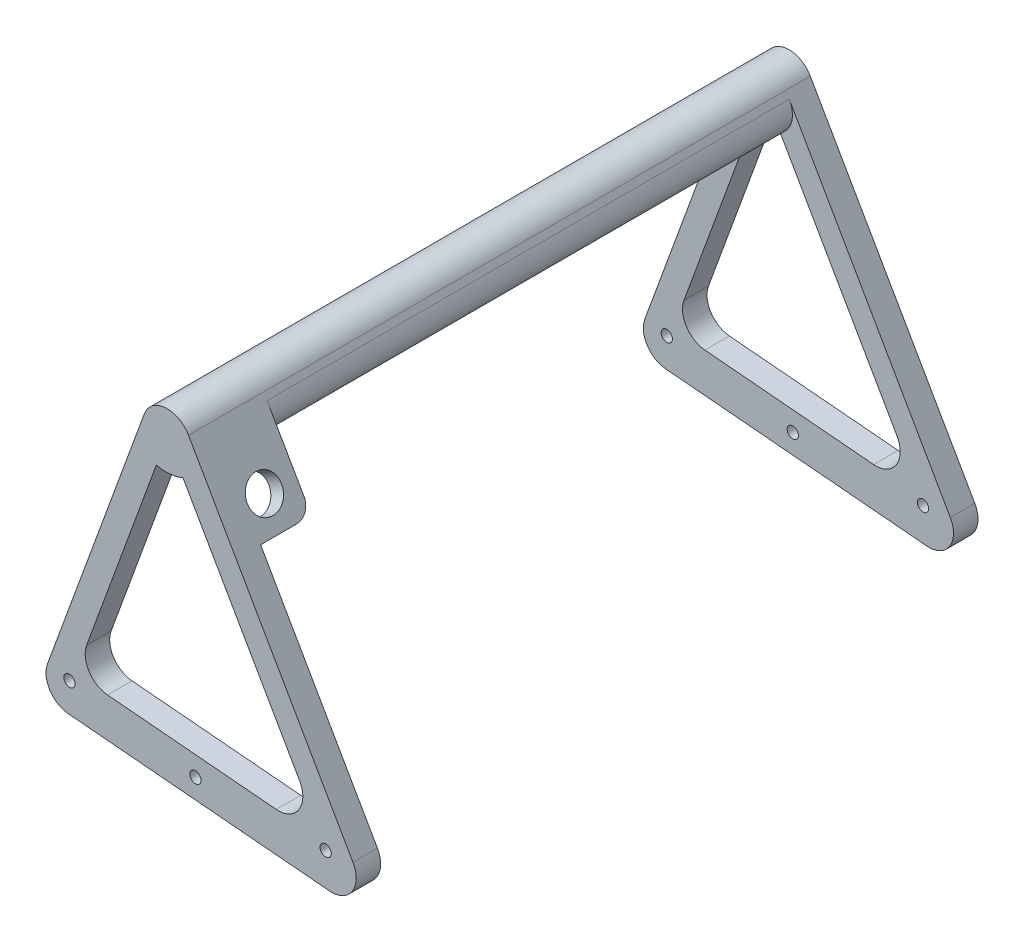
SolidWorks part; units mm, degrees
ref_plane "Ebene vorne" through (0, 0, 0) normal (0, 0, 1) x (1, 0, 0)
ref_plane "Ebene oben" through (0, 0, 0) normal (0, 1, 0) x (1, 0, 0)
ref_plane "Ebene rechts" through (0, 0, 0) normal (1, 0, 0) x (0, 0, -1)
sketch "Skizze1" plane through (0, 0, 0) normal (0, 0, 1) x (1, 0, 0)
  line L0 (-19.2398, 13.5756) -> (6.4562, 83.8896)
  line L1 (6.4562, 83.8896) -> (50.1306, 7.5064)
  line L2 (50.1306, 7.5064) -> (-19.2398, 13.5756)
  line L3 (-11.2375, 20.906) -> (7.458, 72.0643)
  line L4 (7.458, 72.0643) -> (39.2342, 16.4903)
  line L5 (39.2342, 16.4903) -> (-11.2375, 20.906)
  line L8 (-59.2271, -37.2786) -> (110.126, -52.095) construction
  dimension "D1" = 5
  dimension "D2" = 5
  dimension "D3" = 8
extrude "Aufsatz-Linear austragen1" add sketch "Skizze1" along normal blind 5
sketch "Skizze2" plane through (0, 0, -117) normal (0, 0, -1) x (-1, 0, 0)
  line L0 (-50.1306, 7.5064) -> (19.2398, 13.5756)
  line L1 (19.2398, 13.5756) -> (-6.4562, 83.8896)
  line L2 (-6.4562, 83.8896) -> (-50.1306, 7.5064)
  line L3 (-39.2342, 16.4903) -> (11.2375, 20.906)
  line L4 (11.2375, 20.906) -> (-7.458, 72.0643)
  line L5 (-7.458, 72.0643) -> (-39.2342, 16.4903)
extrude "Aufsatz-Linear austragen2" add sketch "Skizze2" along normal blind 5
sketch "Skizze3" plane through (0, 0, 5) normal (0, 0, 1) x (1, 0, 0)
  line L0 (6.4562, 83.8896) -> (-0.4087, 65.1047)
  line L4 (50.1306, 7.5064) -> (6.4562, 83.8896) construction
  line L5 (16.3835, 66.5274) -> (6.4562, 83.8896)
  line L6 (16.3835, 66.5274) -> (-0.4087, 65.1047)
  line L8 (6.4562, 83.8896) -> (-19.2398, 13.5756) construction
  dimension "D1" = 20
  dimension "D2" = 20
extrude "Aufsatz-Linear austragen3" add sketch "Skizze3" against normal through all
fillet "Verrundung1" radius 5 8 edges at (39.2342, 16.4903, 2.5) (-11.2375, 20.906, 2.5) (-11.2375, 20.906, -119.5) (50.1306, 7.5064, -119.5) (39.2342, 16.4903, -119.5) (-19.2398, 13.5756, -119.5) (-19.2398, 13.5756, 2.5) (50.1306, 7.5064, 2.5)
sketch "Skizze4" plane through (0, 0, 5) normal (0, 0, 1) x (1, 0, 0)
  line L0 (13.9446, 21.1239) -> (12.9412, 7.4943) construction
  line L1 (-16.5227, 15.3041) -> (-8.5204, 22.6346) construction
  line L2 (34.3616, 19.6088) -> (45.258, 10.625) construction
  line L3 (1.1405, 21.7125) -> (-1.0929, 8.0856) construction
  line L4 (12.4885, 18.8303) -> (13.9356, 10.6731) construction
  line L5 (-4.7375, 20.3373) -> (29.7145, 17.3232) construction
  line L6 (-12.7398, 13.0069) -> (40.6109, 8.3393) construction
  circle A0 centre (-12.5215, 18.9693) radius 1.15
  circle A1 centre (39.8098, 15.1169) radius 1.15
  arc A2 (-17.0002, 19.7041) -> (-12.7398, 13.0069) centre (-12.304, 17.9879) ccw construction
  arc A3 (-8.9979, 27.0345) -> (-4.7375, 20.3373) centre (-4.3017, 25.3183) ccw construction
  arc A4 (29.7145, 17.3232) -> (34.4908, 24.786) centre (30.1503, 22.3041) ccw construction
  arc A5 (40.6109, 8.3393) -> (45.3873, 15.8021) centre (41.0467, 13.3203) ccw construction
  circle A6 centre (13.2121, 14.7517) radius 1.15
  dimension "D1" = 2.3
extrude "Schnitt-Linear austragen1" cut sketch "Skizze4" against normal through all
fillet "Verrundung2" radius 5 3 edges at (6.4562, 83.8896, -58.5) (-0.4087, 65.1047, -58.5) (16.3835, 66.5274, -58.5)
sketch "Skizze5" plane through (41.0138, 23.4509, 0) normal (0.8681, 0.4964, 0) x (0, 0, -1)
  line L1 (0, 57.4569) -> (10.359, 57.4569)
  line L2 (0, 57.4569) -> (0, 39.2569)
  line L3 (0, 39.2569) -> (10.359, 39.2569)
  line L4 (10.359, 57.4569) -> (10.359, 39.2569)
  line L5 (1.001, 39.2569) -> (6.859, 39.2569) construction
  line L6 (7.359, 39.7569) -> (7.359, 51.4569) construction
  dimension "D1" = 3
extrude "Aufsatz-Linear austragen4" add sketch "Skizze5" against normal up to surface (3 mm away)
sketch "Skizze6" plane through (41.0138, 23.4509, 0) normal (0.8681, 0.4964, 0) x (0, 0, -1)
  circle A0 centre (3.93, 45.6069) radius 3.5
  dimension "D1" = 7
extrude "Schnitt-Linear austragen2" cut sketch "Skizze6" against normal through all
fillet "Verrundung4" radius 3 1 edges at (20.2258, 56.7857, -10.359)
equation "\"M2EinschmelzGewindeDurchmesser\"=3.4"
equation "\"M2EinschmelzGewindeTiefe\"= 4.0"
equation "\"M3EinschmelzGewindeDurchmesser\"= 4.2"
equation "\"M3EinschmelzGewindeTief\"= 5.7"
equation "\"M2SchraubeLoch\"=2.3"
equation "\"M3SchraubeLoch\"=3.3"
equation "\"offSetVonGummiReifen\"= 3.0"
equation "\"D1@Skizze4\"=\"M2SchraubeLoch\""
